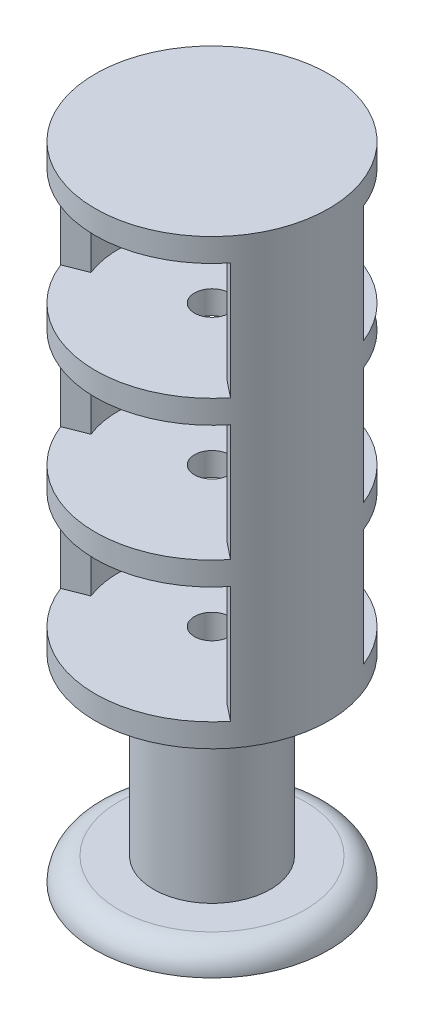
SolidWorks part; units mm, degrees
ref_plane "Front Plane" through (0, 0, 0) normal (0, 0, 1) x (1, 0, 0)
ref_plane "Top Plane" through (0, 0, 0) normal (0, 1, 0) x (1, 0, 0)
ref_plane "Right Plane" through (0, 0, 0) normal (1, 0, 0) x (0, 0, -1)
sketch "Croquis1" plane through (0, 0, 0) normal (0, 1, 0) x (1, 0, 0)
  circle A0 centre (0, 0) radius 5
  circle A1 centre (0, 0) radius 10
  dimension "D1" = 10
  dimension "D2" = 20
extrude "Saliente-Extruir1" add sketch "Croquis1" along normal blind 15 contours A0 region at (0, 0, 0)
extrude "Saliente-Extruir2" add sketch "Croquis1<3>" against normal blind 2 separate body contours A1 A0 region at (-9.7172, 0, 0)
sketch "Croquis1<3>" plane through (0, 0, 0) normal (0, 1, 0) x (1, 0, 0) same geometry as "Croquis1"
sketch "Croquis2" plane through (0, 15, 0) normal (0, 1, 0) x (1, 0, 0)
  circle A0 centre (0, 0) radius 10
  dimension "D1" = 20
extrude "Saliente-Extruir3" add sketch "Croquis2" along normal blind 2
sketch "Croquis3" plane through (0, 17, 0) normal (0, 1, 0) x (1, 0, 0)
  line L0 (-7.8176, 6.2358) -> (7.8176, -6.2358)
  line L1 (9.3091, 3.6524) -> (-9.3091, -3.6524)
  circle A0 centre (0, 0) radius 10
  circle A1 centre (0, 0) radius 8
  circle M3 centre (0, 0) radius 10
  dimension "D1" = 20
  dimension "D3" = 16
  dimension "D2" = 60
extrude "Saliente-Extruir4" add sketch "Croquis3" along normal blind 10 contours A1 L0 L1 M3 | A1 L0 L1 M3 region at (-8.5332, 17, -1.2872) region at (8.5332, 17, 1.2872)
sketch "Croquis4" plane through (0, 27, 0) normal (0, 1, 0) x (1, 0, 0)
  circle A0 centre (0, 0) radius 10
  dimension "D1" = 20
extrude "Saliente-Extruir5" add sketch "Croquis4" along normal blind 2
extrude "Saliente-Extruir6" add sketch "Croquis3<3>" along normal blind 10 from surface contours A1 L0 L1 M3 | A1 L0 L1 M3 region at (-8.5332, 17, -1.2872) region at (8.5332, 17, 1.2872) starting at face at (0, 29, 10)
sketch "Croquis3<3>" plane through (0, 17, 0) normal (0, 1, 0) x (1, 0, 0) same geometry as "Croquis3"
sketch "Croquis5" plane through (0, 39, 0) normal (0, 1, 0) x (1, 0, 0)
  circle A0 centre (0, 0) radius 10
  dimension "D1" = 20
extrude "Saliente-Extruir7" add sketch "Croquis5" along normal blind 2
extrude "Saliente-Extruir8" add sketch "Croquis3<4>" along normal blind 10 from surface contours A1 L0 L1 M3 | A1 L0 L1 M3 region at (-8.5332, 17, -1.2872) region at (8.5332, 17, 1.2872) starting at face at (0, 41, 10)
sketch "Croquis3<4>" plane through (0, 17, 0) normal (0, 1, 0) x (1, 0, 0) same geometry as "Croquis3"
sketch "Croquis7" plane through (0, 51, 0) normal (0, 1, 0) x (1, 0, 0)
  line L0 (-7.8176, 6.2358) -> (7.8176, -6.2358) construction
  circle A0 centre (0, 0) radius 10
extrude "Saliente-Extruir9" add sketch "Croquis7" along normal blind 2
sketch "Croquis9" plane through (0, 0, 0) normal (0, -1, 0) x (1, 0, 0)
  circle A0 centre (0, 0) radius 1.5
  dimension "D1" = 3
extrude "Cortar-Extruir1" cut sketch "Croquis9" against normal up to surface (51 mm away) up to face at (0, 51, 0)
sketch "Croquis10" plane through (0, 0, 0) normal (0, -1, 0) x (1, 0, 0)
  circle A1 centre (0, 0) radius 1.5
  circle A2 centre (0, 0) radius 1.5
  circle M2 centre (0, 0) radius 1.5
  circle M3 centre (0, 0) radius 5
  dimension "D1" = 0
extrude "Saliente-Extruir10" add sketch "Croquis10" along normal up to surface (2 mm away) contours M3 M2 region at (-4.8586, 0, 0) up to face at (0, -2, 5)
sketch "Croquis11" plane through (0, -2, 0) normal (0, -1, 0) x (1, 0, 0)
  circle A0 centre (0, 0) radius 2.5
  dimension "D1" = 5
extrude "Cortar-Extruir2" cut sketch "Croquis11" against normal offset from surface (15 mm away) 2 up to face at (0, 15, 5)
fillet "Redondeo1" radius 2 1 edges at (0, 0, 10)
